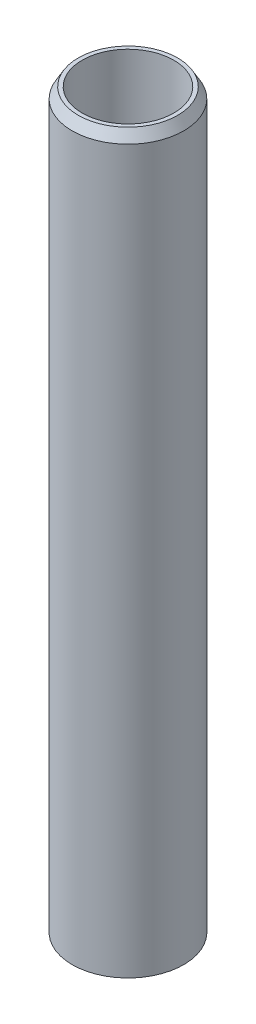
SolidWorks part; units mm, degrees
ref_plane "Front Plane" through (0, 0, 0) normal (0, 0, 1) x (1, 0, 0)
ref_plane "Top Plane" through (0, 0, 0) normal (0, 1, 0) x (1, 0, 0)
ref_plane "Right Plane" through (0, 0, 0) normal (1, 0, 0) x (0, 0, -1)
sketch "Sketch1" plane through (0, 0, 0) normal (0, 1, 0) x (1, 0, 0)
  circle A0 centre (0, 0) radius 25
  dimension "SHAFT_OD" = 50
extrude "Boss-Extrude1" add sketch "Sketch1" along normal blind 331.0605
sketch "Sketch2" plane through (0, 0, 0) normal (0, 1, 0) x (1, 0, 0)
  circle A0 centre (0, 0) radius 20.5414
  dimension "BORE_D" = 41.0828
extrude "Cut-Extrude1" cut sketch "Sketch2" along normal through all
chamfer "Chamfer1" distance 4.6903 angle 30 2 edges at (0, 331.0605, 25) (0, 0, 25) first distance on face at (0, 331.0605, 25) first distance on face at (0, 0, 20.5414)
